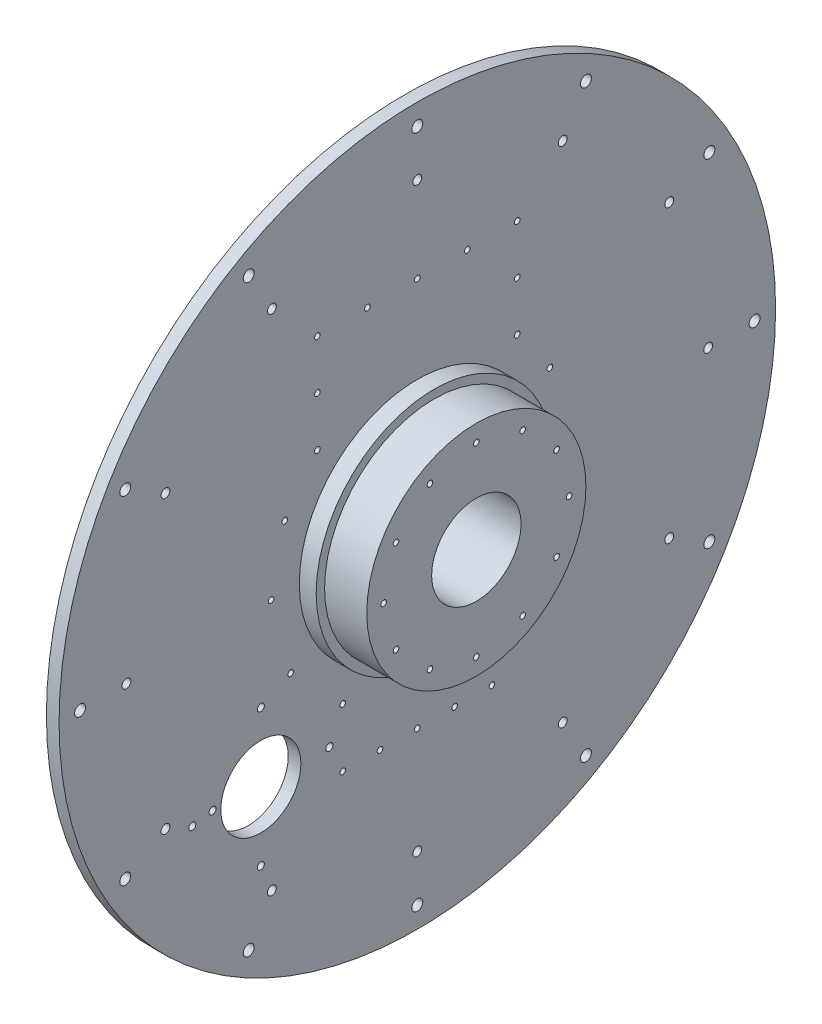
SolidWorks part; units mm, degrees
ref_plane "Front Plane" through (0, 0, 0) normal (0, 0, 1) x (1, 0, 0)
ref_plane "Top Plane" through (0, 0, 0) normal (0, 1, 0) x (1, 0, 0)
ref_plane "Right Plane" through (0, 0, 0) normal (1, 0, 0) x (0, 0, -1)
sketch "Sketch1" plane through (0, 0, 0) normal (0, 0, 1) x (1, 0, 0)
  line L0 (0, 425) -> (0, 0)
  line L1 (0, 0) -> (15, 0)
  line L2 (15, 0) -> (15, 425)
  line L3 (15, 425) -> (0, 425)
  line L4 (0, 0) -> (15, 0) construction
revolve "Revolve1" add sketch "Sketch1" angle 360 about L4 reverse direction yes
sketch "Sketch2" plane through (15, 0, 0) normal (1, 0, 0) x (0, 0, -1)
  circle A0 centre (0, 0) radius 140
extrude "Boss-Extrude1" add sketch "Sketch2" along normal blind 20
sketch "Sketch3" plane through (35, 0, 0) normal (1, 0, 0) x (0, 0, -1)
  circle A0 centre (0, 0) radius 130
extrude "Boss-Extrude2" add sketch "Sketch3" along normal blind 50
sketch "Sketch4" plane through (0, 0, 0) normal (-1, 0, 0) x (0, 0, 1)
  circle A0 centre (0, 0) radius 85
extrude "Boss-Extrude3" add sketch "Sketch4" along normal blind 23
ref_plane "Plane1" through (0, 0, 0) normal (0, 0, -1) x (-1, 0, 0)
sketch "Sketch5" plane through (0, 0, 0) normal (0, 0, -1) x (-1, 0, 0)
  line L0 (-85, 113.3235) -> (-85, 110)
  line L1 (-85, 110) -> (-67, 110)
  line L2 (-67, 110) -> (-68.997, 113.3235)
  line L3 (-68.997, 113.3235) -> (-73, 113.3235)
  line L4 (-73, 113.3235) -> (-85, 113.3235)
  line L5 (-85, 110) -> (-67, 110) construction
revolve "Cut-Revolve1" cut sketch "Sketch5" angle 360 about L5 reverse direction yes
ref_plane "Plane2" through (0, 0, -55) normal (0, 0, -1) x (-1, 0, 0)
sketch "Sketch6" plane through (0, 0, -55) normal (0, 0, -1) x (-1, 0, 0)
  line L0 (-85, 98.5863) -> (-85, 95.2628)
  line L1 (-85, 95.2628) -> (-67, 95.2628)
  line L2 (-67, 95.2628) -> (-68.997, 98.5863)
  line L3 (-68.997, 98.5863) -> (-73, 98.5863)
  line L4 (-73, 98.5863) -> (-85, 98.5863)
  line L5 (-85, 95.2628) -> (-67, 95.2628) construction
revolve "Cut-Revolve2" cut sketch "Sketch6" angle 360 about L5 reverse direction yes
ref_plane "Plane3" through (0, 0, -95.2628) normal (0, 0, -1) x (-1, 0, 0)
sketch "Sketch7" plane through (0, 0, -95.2628) normal (0, 0, -1) x (-1, 0, 0)
  line L0 (-85, 58.3235) -> (-85, 55)
  line L1 (-85, 55) -> (-67, 55)
  line L2 (-67, 55) -> (-68.997, 58.3235)
  line L3 (-68.997, 58.3235) -> (-73, 58.3235)
  line L4 (-73, 58.3235) -> (-85, 58.3235)
  line L5 (-85, 55) -> (-67, 55) construction
revolve "Cut-Revolve3" cut sketch "Sketch7" angle 360 about L5 reverse direction yes
ref_plane "Plane4" through (0, 0, -110) normal (0, 0, -1) x (-1, 0, 0)
sketch "Sketch8" plane through (0, 0, -110) normal (0, 0, -1) x (-1, 0, 0)
  line L0 (-85, 3.3235) -> (-85, 0)
  line L1 (-85, 0) -> (-67, 0)
  line L2 (-67, 0) -> (-68.997, 3.3235)
  line L3 (-68.997, 3.3235) -> (-73, 3.3235)
  line L4 (-73, 3.3235) -> (-85, 3.3235)
  line L5 (-85, 0) -> (-67, 0) construction
revolve "Cut-Revolve4" cut sketch "Sketch8" angle 360 about L5 reverse direction yes
sketch "Sketch9" plane through (0, 0, -95.2628) normal (0, 0, -1) x (-1, 0, 0)
  line L0 (-85, -51.6765) -> (-85, -55)
  line L1 (-85, -55) -> (-67, -55)
  line L2 (-67, -55) -> (-68.997, -51.6765)
  line L3 (-68.997, -51.6765) -> (-73, -51.6765)
  line L4 (-73, -51.6765) -> (-85, -51.6765)
  line L5 (-85, -55) -> (-67, -55) construction
revolve "Cut-Revolve5" cut sketch "Sketch9" angle 360 about L5 reverse direction yes
sketch "Sketch10" plane through (0, 0, -55) normal (0, 0, -1) x (-1, 0, 0)
  line L0 (-85, -91.9393) -> (-85, -95.2628)
  line L1 (-85, -95.2628) -> (-67, -95.2628)
  line L2 (-67, -95.2628) -> (-68.997, -91.9393)
  line L3 (-68.997, -91.9393) -> (-73, -91.9393)
  line L4 (-73, -91.9393) -> (-85, -91.9393)
  line L5 (-85, -95.2628) -> (-67, -95.2628) construction
revolve "Cut-Revolve6" cut sketch "Sketch10" angle 360 about L5 reverse direction yes
sketch "Sketch11" plane through (0, 0, 0) normal (0, 0, -1) x (-1, 0, 0)
  line L0 (-85, -106.6765) -> (-85, -110)
  line L1 (-85, -110) -> (-67, -110)
  line L2 (-67, -110) -> (-68.997, -106.6765)
  line L3 (-68.997, -106.6765) -> (-73, -106.6765)
  line L4 (-73, -106.6765) -> (-85, -106.6765)
  line L5 (-85, -110) -> (-67, -110) construction
revolve "Cut-Revolve7" cut sketch "Sketch11" angle 360 about L5 reverse direction yes
ref_plane "Plane5" through (0, 0, 55) normal (0, 0, -1) x (-1, 0, 0)
sketch "Sketch12" plane through (0, 0, 55) normal (0, 0, -1) x (-1, 0, 0)
  line L0 (-85, -91.9393) -> (-85, -95.2628)
  line L1 (-85, -95.2628) -> (-67, -95.2628)
  line L2 (-67, -95.2628) -> (-68.997, -91.9393)
  line L3 (-68.997, -91.9393) -> (-73, -91.9393)
  line L4 (-73, -91.9393) -> (-85, -91.9393)
  line L5 (-85, -95.2628) -> (-67, -95.2628) construction
revolve "Cut-Revolve8" cut sketch "Sketch12" angle 360 about L5 reverse direction yes
ref_plane "Plane6" through (0, 0, 95.2628) normal (0, 0, -1) x (-1, 0, 0)
sketch "Sketch13" plane through (0, 0, 95.2628) normal (0, 0, -1) x (-1, 0, 0)
  line L0 (-85, -51.6765) -> (-85, -55)
  line L1 (-85, -55) -> (-67, -55)
  line L2 (-67, -55) -> (-68.997, -51.6765)
  line L3 (-68.997, -51.6765) -> (-73, -51.6765)
  line L4 (-73, -51.6765) -> (-85, -51.6765)
  line L5 (-85, -55) -> (-67, -55) construction
revolve "Cut-Revolve9" cut sketch "Sketch13" angle 360 about L5 reverse direction yes
ref_plane "Plane7" through (0, 0, 110) normal (0, 0, -1) x (-1, 0, 0)
sketch "Sketch14" plane through (0, 0, 110) normal (0, 0, -1) x (-1, 0, 0)
  line L0 (-85, 3.3235) -> (-85, 0)
  line L1 (-85, 0) -> (-67, 0)
  line L2 (-67, 0) -> (-68.997, 3.3235)
  line L3 (-68.997, 3.3235) -> (-73, 3.3235)
  line L4 (-73, 3.3235) -> (-85, 3.3235)
  line L5 (-85, 0) -> (-67, 0) construction
revolve "Cut-Revolve10" cut sketch "Sketch14" angle 360 about L5 reverse direction yes
sketch "Sketch15" plane through (0, 0, 95.2628) normal (0, 0, -1) x (-1, 0, 0)
  line L0 (-85, 58.3235) -> (-85, 55)
  line L1 (-85, 55) -> (-67, 55)
  line L2 (-67, 55) -> (-68.997, 58.3235)
  line L3 (-68.997, 58.3235) -> (-73, 58.3235)
  line L4 (-73, 58.3235) -> (-85, 58.3235)
  line L5 (-85, 55) -> (-67, 55) construction
revolve "Cut-Revolve11" cut sketch "Sketch15" angle 360 about L5 reverse direction yes
sketch "Sketch16" plane through (0, 0, 55) normal (0, 0, -1) x (-1, 0, 0)
  line L0 (-85, 98.5863) -> (-85, 95.2628)
  line L1 (-85, 95.2628) -> (-67, 95.2628)
  line L2 (-67, 95.2628) -> (-68.997, 98.5863)
  line L3 (-68.997, 98.5863) -> (-73, 98.5863)
  line L4 (-73, 98.5863) -> (-85, 98.5863)
  line L5 (-85, 95.2628) -> (-67, 95.2628) construction
revolve "Cut-Revolve12" cut sketch "Sketch16" angle 360 about L5 reverse direction yes
hole_wizard "1/4 Clearance Hole1" positions "Sketch18" profile "Sketch17" hole size "1/4" standard "ANSI Inch"
sketch "Sketch18" plane through (0, 0, 0) normal (-1, 0, 0) x (0, 0, 1)
  point P0 (88.5, -218.5)
  point P1 (88.5, -149.2314)
  point P2 (44.25, -218.5)
  point P3 (0, -218.5)
  point P4 (-44.25, -218.5)
  point P5 (150.2554, -86.75)
  point P6 (-88.5, -218.5)
  point P7 (-88.5, -149.2314)
  point P8 (-173.5, 0)
  point P9 (-150.2554, -86.75)
  point P10 (-157.2444, 73.3243)
  point P11 (-118.5, 126.7281)
  point P12 (-118.5, 185.114)
  point P13 (-118.5, 243.5)
  point P14 (-59.25, 243.5)
  point P15 (0, 243.5)
  point P16 (59.25, 243.5)
  point P17 (118.5, 243.5)
  point P18 (118.5, 185.114)
  point P19 (118.5, 126.7281)
  point P20 (157.2444, 73.3243)
  point P21 (173.5, 0)
sketch "Sketch17" plane through (0, -218.5, 88.5) normal (0, 1, 0) x (0, 0, 1)
  line L0 (0, 0) -> (0, 85)
  line L1 (0, 85) -> (3.3235, 85)
  line L2 (3.3235, 85) -> (3.3235, 0)
  line L5 (3.3235, 0) -> (0, 0)
  line L11 (0, -6.35) -> (0, 107.95) construction
  dimension "Thru Hole Dia." = 6.647
  dimension "Thru Hole Depth" = 85
hole_wizard "Hole1" positions "Sketch20" profile "Sketch19" legacy
sketch "Sketch20" plane through (0, 0, 0) normal (-1, 0, 0) x (0, 0, 1)
  point P0 (400, 0)
  point P1 (346.4102, -200)
  point P2 (200, -346.4102)
  point P3 (0, -400)
  point P4 (-200, -346.4102)
  point P5 (-346.4102, -200)
  point P6 (-400, 0)
  point P7 (-346.4102, 200)
  point P8 (-200, 346.4102)
  point P9 (0, 400)
  point P10 (200, 346.4102)
  point P11 (346.4102, 200)
sketch "Sketch19" plane through (0, 0, 400) normal (0, 1, 0) x (0, 0, 1)
  line L0 (0, 0) -> (0, 88.9056)
  line L1 (0, 88.9056) -> (6.5, 85)
  line L2 (6.5, 85) -> (6.5, 0)
  line L4 (6.5, 0) -> (0, 0)
  line L6 (0, 88.9056) -> (-6.5, 85) construction
  line L7 (0, -4.2442) -> (0, 117.3081) construction
  dimension "Diameter" = 13
  dimension "Depth" = 85
  dimension "Drill Angle" = 118
hole_wizard "Hole2" positions "Sketch22" profile "Sketch21" legacy
sketch "Sketch22" plane through (0, 0, 0) normal (-1, 0, 0) x (0, 0, 1)
  point P0 (0, -345)
  point P1 (-172.5, -298.7788)
  point P2 (-298.7788, -172.5)
  point P3 (-345, 0)
  point P4 (-298.7788, 172.5)
  point P5 (-172.5, 298.7788)
  point P6 (0, 345)
  point P7 (172.5, 298.7788)
  point P8 (298.7788, 172.5)
  point P9 (345, 0)
  point P10 (298.7788, -172.5)
  point P11 (172.5, -298.7788)
sketch "Sketch21" plane through (0, -345, 0) normal (0, 1, 0) x (0, 0, 1)
  line L0 (0, 0) -> (0, 88.1545)
  line L1 (0, 88.1545) -> (5.25, 85)
  line L2 (5.25, 85) -> (5.25, 0)
  line L4 (5.25, 0) -> (0, 0)
  line L6 (0, 88.1545) -> (-5.25, 85) construction
  line L7 (0, -4.2442) -> (0, 117.3081) construction
  dimension "Diameter" = 10.5
  dimension "Depth" = 85
  dimension "Drill Angle" = 118
hole_wizard "5/16 Clearance Hole1" positions "Sketch24" profile "Sketch23" hole size "5/16" standard "ANSI Inch"
sketch "Sketch24" plane through (0, 0, 0) normal (-1, 0, 0) x (0, 0, 1)
  line L0 (266.9328, -185.6155) -> (185.6155, -104.2983) construction
  line L1 (185.6155, -104.2983) -> (104.2983, -185.6155) construction
  line L2 (104.2983, -185.6155) -> (185.6155, -266.9328) construction
  line L3 (185.6155, -266.9328) -> (266.9328, -185.6155) construction
  circle A0 centre (185.6155, -185.6155) radius 57.5
  point P0 (266.9328, -185.6155)
  point P1 (185.6155, -266.9328)
  point P2 (104.2983, -185.6155)
  point P3 (185.6155, -104.2983)
  point P22 (185.6155, -185.6155)
  point P23 (242.9743, -181.5878)
  dimension "D3" = 115
sketch "Sketch23" plane through (0, -185.6155, 266.9328) normal (0, 1, 0) x (0, 0, 1)
  line L0 (0, 0) -> (0, 85)
  line L1 (0, 85) -> (4.188, 85)
  line L2 (4.188, 85) -> (4.188, 0)
  line L5 (4.188, 0) -> (0, 0)
  line L11 (0, -6.35) -> (0, 107.95) construction
  dimension "Thru Hole Dia." = 8.376
  dimension "Thru Hole Depth" = 85
hole_wizard "Hole3" positions "Sketch26" profile "Sketch25" legacy
sketch "Sketch26" plane through (15, 0, 0) normal (1, 0, 0) x (0, 0, -1)
  point P0 (-185.6155, -185.6155)
sketch "Sketch25" plane through (15, -185.6155, 185.6155) normal (0, 1, 0) x (0, 0, -1)
  line L0 (0, 0) -> (0, 38)
  line L1 (0, 38) -> (47.5, 38)
  line L2 (47.5, 38) -> (47.5, 0)
  line L3 (47.5, 0) -> (0, 0)
  line L4 (0, 110) -> (0, -10) construction
  dimension "Diameter" = 95
  dimension "Depth" = 38
hole_wizard "Hole4" positions "Sketch28" profile "Sketch27" legacy
sketch "Sketch28" plane through (-23, 0, 0) normal (-1, 0, 0) x (0, 0, 1)
  point P0 (0, 0)
sketch "Sketch27" plane through (-23, 0, 0) normal (0, 1, 0) x (0, 0, 1)
  line L0 (0, 0) -> (0, 108)
  line L1 (0, 108) -> (53, 108)
  line L2 (53, 108) -> (53, 28.98)
  line L3 (53, 28.98) -> (60, 28.98)
  line L4 (60, 28.98) -> (60, 0)
  line L5 (60, 0) -> (0, 0)
  line L6 (0, 110) -> (0, -10) construction
  dimension "Diameter" = 106
  dimension "Depth" = 108
  dimension "C-Bore Diameter" = 120
  dimension "C-Bore Depth" = 28.98
ref_axis "Axis1" through (503.2772, 0, 0) along (-1, 0, 0)
